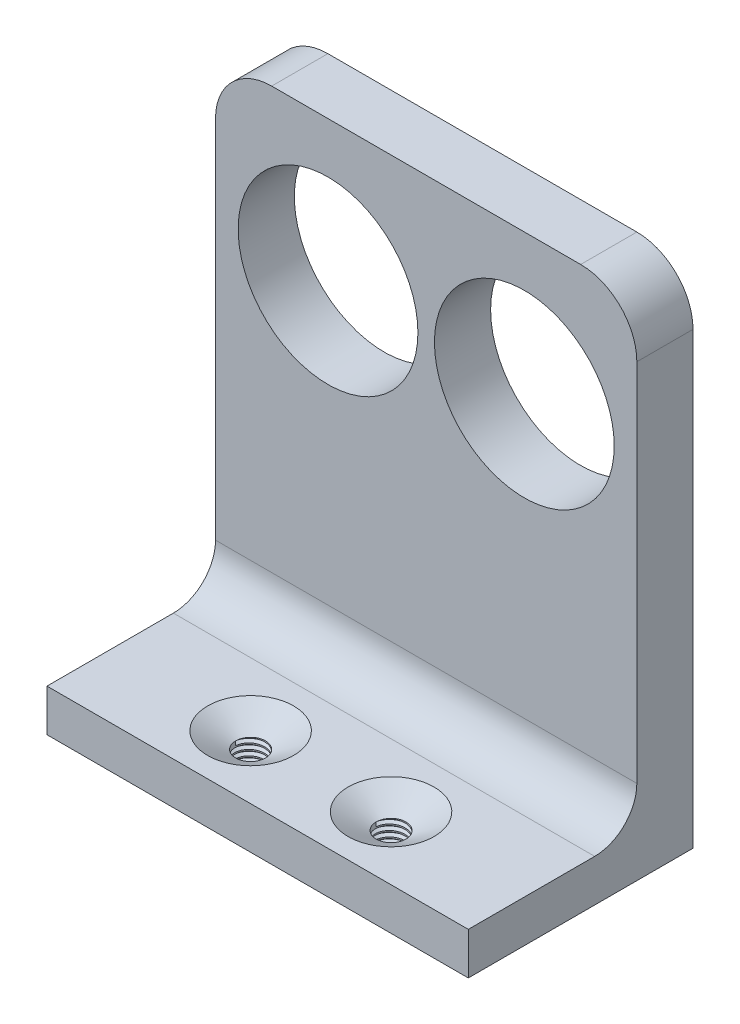
SolidWorks part; units mm, degrees
ref_plane "Front Plane" through (0, 0, 0) normal (0, 0, 1) x (1, 0, 0)
ref_plane "Top Plane" through (0, 0, 0) normal (0, 1, 0) x (1, 0, 0)
ref_plane "Right Plane" through (0, 0, 0) normal (1, 0, 0) x (0, 0, -1)
sketch "Sketch1" plane through (0, 0, 0) normal (0, 0, 1) x (1, 0, 0)
  line L1 (-37.5, 45) -> (37.5, 45)
  line L2 (-37.5, 45) -> (-37.5, -45)
  line L3 (-37.5, -45) -> (37.5, -45)
  line L4 (37.5, 45) -> (37.5, -45)
  line L5 (0, -45) -> (0, 45) construction
  line L6 (-37.5, 0) -> (37.5, 0) construction
  point P0 (0, 0)
  dimension "D1" = 75
  dimension "D2" = 90
extrude "Boss-Extrude1" add sketch "Sketch1" along normal blind 10
sketch "Sketch2" plane through (0, 0, 0) normal (0, 0, 1) x (1, 0, 0)
  circle A0 centre (-17.4702, 20) radius 16
  circle A2 centre (17.4702, 20) radius 16
extrude "Cut-Extrude1" cut sketch "Sketch2" along normal blind 28 contours A0 | A2
fillet "Fillet1" radius 10 2 edges at (37.5, 45, 5) (-37.5, 45, 5)
sketch "Sketch3" plane through (0, 0, 10) normal (0, 0, 1) x (1, 0, 0)
  line L0 (-37.5, 35) -> (-37.5, -45) construction
  line L1 (-37.5, -37.5) -> (37.5, -37.5)
  line L2 (-37.5, -37.5) -> (-37.5, -45)
  line L3 (-37.5, -45) -> (37.5, -45)
  line L4 (37.5, -37.5) -> (37.5, -45)
  dimension "D1" = 7.5
extrude "Boss-Extrude2" add sketch "Sketch3" along normal blind 30
fillet "Fillet2" radius 7.5 1 edges at (0, -37.5, 10)
sketch "Sketch4" plane through (0, -37.5, 0) normal (0, 1, 0) x (1, 0, 0)
  circle A1 centre (-12.5, -28.75) radius 2.65
  circle A3 centre (12.5, -28.75) radius 2.65
extrude "Cut-Extrude2" cut sketch "Sketch4" against normal blind 30
chamfer "Chamfer1" distance 5 angle 30 1 edges at (-12.5, -37.5, 26.1) first distance on face at (12.5, -37.5, 31.4)
thread "Thread3" pitch 1 method cut profile "Thread Profile3" start angle 0, offset 0, length 20, pitch 1, diameter 5.3
ref_plane "Plane3" through (-15.15, -40.3868, 28.75) normal (0, 0, 1) x (-1, 0, 0)
sketch "Thread Profile3" plane through (-15.15, -40.3868, 28.75) normal (0, 0, 1) x (-1, 0, 0)
  line L0 (0, 0) -> (0, 1) construction
  line L1 (0, 0) -> (0.5413, 0.3125)
  line L2 (0.5413, 0.3125) -> (0.5413, 0.4375)
  line L3 (0.5413, 0.4375) -> (0, 0.75)
  line L4 (0.5413, 0.375) -> (0, 0.375) construction
  line L11 (0, 0) -> (0, 0.75)
  point P2 (0, 0)
  dimension "Pitch" = 1
  dimension "Profile_Angle" = 60
  dimension "Profile_Land" = 0.125
  dimension "Profile_Height" = 0.5413
chamfer "Chamfer3" distance 5 angle 30 1 edges at (12.5, -37.5, 31.4) first distance on face at (-12.5, -37.5, 21.1)
thread "Thread5" pitch 1 method cut profile "Thread Profile5" start angle 0, offset 0, length 20, pitch 1, diameter 5.3
ref_plane "Plane5" through (9.85, -40.3868, 28.75) normal (0, 0, 1) x (-1, 0, 0)
sketch "Thread Profile5" plane through (9.85, -40.3868, 28.75) normal (0, 0, 1) x (-1, 0, 0)
  line L0 (0, 0) -> (0, 1) construction
  line L1 (0, 0) -> (0.5413, 0.3125)
  line L2 (0.5413, 0.3125) -> (0.5413, 0.4375)
  line L3 (0.5413, 0.4375) -> (0, 0.75)
  line L4 (0.5413, 0.375) -> (0, 0.375) construction
  line L11 (0, 0) -> (0, 0.75)
  point P2 (0, 0)
  dimension "Pitch" = 1
  dimension "Profile_Angle" = 60
  dimension "Profile_Land" = 0.125
  dimension "Profile_Height" = 0.5413
